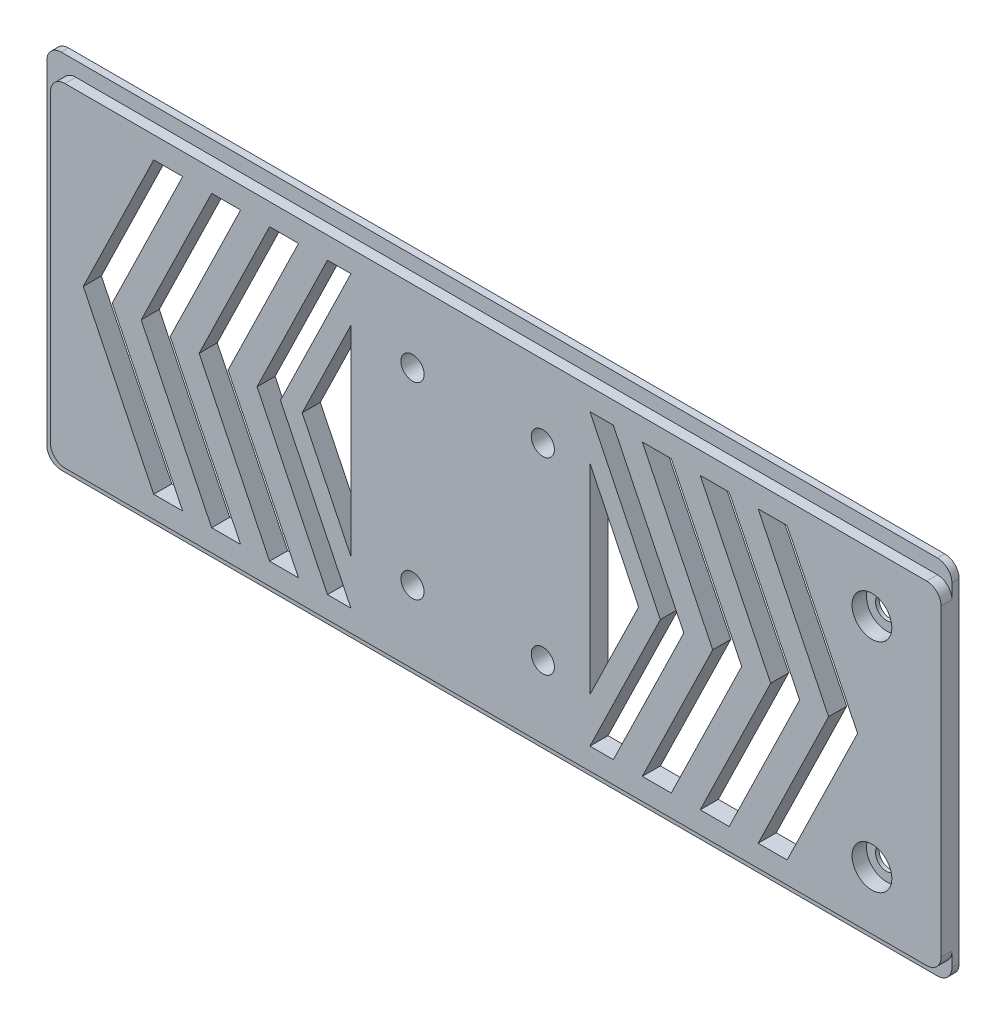
SolidWorks part; units mm, degrees
ref_plane "Plano frontal" through (0, 0, 0) normal (0, 0, 1) x (1, 0, 0)
ref_plane "Plano superior" through (0, 0, 0) normal (0, 1, 0) x (1, 0, 0)
ref_plane "Plano direito" through (0, 0, 0) normal (1, 0, 0) x (0, 0, -1)
sketch "Esboço1" plane through (0, 0, 0) normal (0, 0, 1) x (1, 0, 0)
  line L1 (-17.8424, 34.9053) -> (107.1576, 34.9053)
  line L2 (-17.8424, 34.9053) -> (-17.8424, -15.0947)
  line L3 (-17.8424, -15.0947) -> (107.1576, -15.0947)
  line L4 (107.1576, 34.9053) -> (107.1576, -15.0947)
  dimension "D1" = 50
  dimension "D2" = 125
extrude "Ressalto-extrusão1" add sketch "Esboço1" along normal blind 2.5
sketch "Esboço2" plane through (0, 0, 2.5) normal (0, 0, 1) x (1, 0, 0)
  line L1 (31.1576, 25.9053) -> (55.1576, 25.9053)
  line L2 (31.1576, 25.9053) -> (31.1576, -6.0947)
  line L3 (31.1576, -6.0947) -> (55.1576, -6.0947)
  line L4 (55.1576, 25.9053) -> (55.1576, -6.0947)
  line L8 (107.1576, -15.0947) -> (107.1576, 34.9053) construction
  line L9 (-17.8424, -15.0947) -> (107.1576, -15.0947) construction
  line L10 (43.1576, 25.9053) -> (43.1576, -6.0947) construction
  line L11 (31.1576, 9.9053) -> (43.1576, 9.9053) construction
  line L12 (55.1576, 25.9053) -> (107.1576, 25.9053) construction
  line L15 (55.1576, 25.9053) -> (55.1576, 34.9053) construction
  line L16 (107.1576, 34.9053) -> (-17.8424, 34.9053) construction
  line L17 (55.1576, -6.0947) -> (55.1576, -15.0947) construction
  circle A0 centre (34.1576, 22.9053) radius 1.6
  circle A1 centre (34.1576, -3.0947) radius 1.6
  circle A2 centre (52.1576, -3.0947) radius 1.6
  circle A3 centre (52.1576, 22.9053) radius 1.6
  dimension "D5" = 3
  dimension "D1" = 24
  dimension "D2" = 32
  dimension "D3" = 52
  dimension "D6" = 3
extrude "Corte-extrusão2" cut sketch "Esboço2" against normal blind 2.5 contours A2 | A1 | A3 | A0
sketch "Esboço3" plane through (0, 0, 2.5) normal (0, 0, 1) x (1, 0, 0)
  line L0 (-17.8424, 9.9053) -> (107.1576, 9.9053) construction
  line L1 (-17.8424, 34.9053) -> (-17.8424, -15.0947) construction
  line L2 (107.1576, -15.0947) -> (107.1576, 34.9053) construction
  line L4 (-17.8424, 34.9053) -> (107.1576, 34.9053)
  line L5 (-17.8424, 34.9053) -> (-17.8424, 32.9053)
  line L6 (-15.8424, 32.9053) -> (107.1576, 32.9053)
  line L7 (107.1576, 34.9053) -> (107.1576, 32.9053)
  line L8 (107.1576, -15.0947) -> (107.1576, -13.0947)
  line L9 (-17.8424, -15.0947) -> (107.1576, -15.0947)
  line L10 (-17.8424, -15.0947) -> (-17.8424, -13.0947)
  line L11 (-17.8424, 32.9053) -> (-17.8424, -13.0947)
  line L12 (-17.8424, 34.9053) -> (-15.8424, 34.9053)
  line L13 (-17.8424, 34.9053) -> (-17.8424, -15.0947)
  line L14 (-17.8424, -15.0947) -> (-15.8424, -15.0947)
  line L15 (-15.8424, 32.9053) -> (-15.8424, -13.0947)
  line L16 (-15.8424, -13.0947) -> (107.1576, -13.0947)
  point P18 (-15.8424, 32.9053)
  line M17 (-17.8424, 34.9053) -> (-17.8424, -15.0947)
  line M18 (-17.8424, -15.0947) -> (107.1576, -15.0947)
  line M19 (107.1576, -15.0947) -> (107.1576, 34.9053)
  line M20 (107.1576, 34.9053) -> (-17.8424, 34.9053)
  dimension "D1" = 2
  dimension "D2" = 2
extrude "Corte-extrusão3" cut sketch "Esboço3" against normal blind 1.5 contours L0 L15 L6 L4 M17 M19 M20 | L0 L13 L9 L16 L15 M17 M18 M19 region at (-16.5677, 21.4053, 2.5) region at (-16.8424, 8.6306, 2.5)
sketch "Esboço4" plane through (0, 0, 2.5) normal (0, 0, 1) x (1, 0, 0)
  line L0 (42.1576, 32.9053) -> (42.1576, -13.0947) construction
  line L7 (15.9251, 9.9053) -> (25.654, 29.9053)
  line L16 (15.9251, 9.9053) -> (25.654, -10.0947)
  line L18 (12.6906, 9.9053) -> (22.4196, 29.9053)
  line L19 (22.4196, 29.9053) -> (25.654, 29.9053)
  line L20 (25.654, 23.7382) -> (18.9251, 9.9053)
  line L21 (18.9251, 9.9053) -> (25.654, -3.9275)
  line L24 (-15.8424, 32.9053) -> (-15.8424, -13.0947) construction
  line L25 (8.6906, 9.9053) -> (18.4196, 29.9053)
  line L26 (18.4196, -10.0947) -> (8.6906, 9.9053)
  line L27 (4.6906, 9.9053) -> (14.4196, 29.9053)
  line L28 (14.4196, -10.0947) -> (4.6906, 9.9053)
  line L29 (0.6906, 9.9053) -> (10.4196, 29.9053)
  line L30 (10.4196, -10.0947) -> (0.6906, 9.9053)
  line L31 (-3.3094, 9.9053) -> (6.4196, 29.9053)
  line L32 (6.4196, -10.0947) -> (-3.3094, 9.9053)
  line L33 (-7.3094, 9.9053) -> (2.4196, 29.9053)
  line L34 (2.4196, -10.0947) -> (-7.3094, 9.9053)
  line L35 (-11.3094, 9.9053) -> (-1.5804, 29.9053)
  line L36 (-1.5804, -10.0947) -> (-11.3094, 9.9053)
  line L38 (-12.9532, 9.9053) -> (-11.3094, 9.9053) construction
  line L41 (-1.5804, 29.9053) -> (2.4196, 29.9053)
  line L42 (6.4196, 29.9053) -> (10.4196, 29.9053)
  line L43 (14.4196, 29.9053) -> (18.4196, 29.9053)
  line L46 (-1.5804, -10.0947) -> (2.4196, -10.0947)
  line L47 (6.4196, -10.0947) -> (10.4196, -10.0947)
  line L48 (14.4196, -10.0947) -> (18.4196, -10.0947)
  line L50 (25.654, 23.7382) -> (25.654, -3.9275)
  line L51 (25.654, -3.9275) -> (25.654, 23.7382)
  line L53 (12.6906, 9.9053) -> (22.4196, -10.0947)
  line L54 (85.8956, -10.0947) -> (95.6245, 9.9053)
  line L55 (25.654, -10.0947) -> (22.4196, -10.0947)
  line L57 (14.4196, -10.0947) -> (18.4196, -10.0947)
  line L58 (6.4196, -10.0947) -> (10.4196, -10.0947)
  line L59 (-1.5804, -10.0947) -> (2.4196, -10.0947)
  line L61 (95.6245, 9.9053) -> (85.8956, 29.9053)
  line L62 (85.8956, 29.9053) -> (81.8956, 29.9053)
  line L63 (91.6245, 9.9053) -> (81.8956, 29.9053)
  line L64 (81.8956, -10.0947) -> (91.6245, 9.9053)
  line L65 (85.8956, -10.0947) -> (81.8956, -10.0947)
  line L66 (77.8956, -10.0947) -> (87.6245, 9.9053)
  line L67 (87.6245, 9.9053) -> (77.8956, 29.9053)
  line L68 (77.8956, 29.9053) -> (73.8956, 29.9053)
  line L69 (83.6245, 9.9053) -> (73.8956, 29.9053)
  line L70 (73.8956, -10.0947) -> (83.6245, 9.9053)
  line L71 (77.8956, -10.0947) -> (73.8956, -10.0947)
  line L72 (69.8956, -10.0947) -> (79.6245, 9.9053)
  line L73 (79.6245, 9.9053) -> (69.8956, 29.9053)
  line L74 (69.8956, 29.9053) -> (65.8956, 29.9053)
  line L75 (75.6245, 9.9053) -> (65.8956, 29.9053)
  line L76 (65.8956, -10.0947) -> (75.6245, 9.9053)
  line L77 (69.8956, -10.0947) -> (65.8956, -10.0947)
  line L78 (71.6245, 9.9053) -> (61.8956, 29.9053)
  line L79 (61.8956, 29.9053) -> (58.6611, 29.9053)
  line L80 (68.3901, 9.9053) -> (58.6611, 29.9053)
  line L81 (68.3901, 9.9053) -> (58.6611, -10.0947)
  line L82 (58.6611, -10.0947) -> (61.8956, -10.0947)
  line L83 (71.6245, 9.9053) -> (61.8956, -10.0947)
  line L84 (65.3901, 9.9053) -> (58.6611, -3.9275)
  line L85 (58.6611, 23.7382) -> (65.3901, 9.9053)
  line L86 (58.6611, -3.9275) -> (58.6611, 23.7382)
  line L89 (95.6245, 9.9053) -> (105.5606, 9.9053) construction
  dimension "D3" = 58
  dimension "D1" = 40
  dimension "D2" = 3
extrude "Corte-extrusão5" cut sketch "Esboço4" against normal through all both and the other way through all contours L86 L84 L85 | L83 L78 L79 L80 L81 L82 | L77 L72 L73 L74 L75 L76 | L71 L66 L67 L68 L69 L70 | L65 L54 L61 L62 L63 L64 | L51 L20 L21 | L53 L55 L16 L7 L19 L18 | L48 L26 L25 L43 L27 L28 | L47 L30 L29 L42 L31 L32 | L46 L34 L33 L41 L35 L36 region at (83.8956, -9.6718, 2.5) region at (75.8956, -9.6718, 2.5) region at (67.8956, -9.6718, 2.5) region at (66.3819, 0.0893, 2.5) region at (60.9041, 9.9053, 2.5)
sketch "Esboço12" plane through (0, 0, 2.5) normal (0, 0, 1) x (1, 0, 0)
  line L0 (107.1576, -13.0947) -> (107.1576, 32.9053) construction
  line L1 (-15.8424, 32.9053) -> (107.1576, 32.9053) construction
  line L2 (95.6245, 9.9053) -> (107.1576, 9.9053) construction
  circle A0 centre (97.6076, 24.9053) radius 2.75
  circle A1 centre (97.6076, -5.0947) radius 2.75
  point P0 (97.6076, 24.9053)
  point P8 (97.6076, -5.0947)
  point P13 (94.8576, 24.9053)
  point P14 (94.8576, -5.0947)
  dimension "D3" = 5.5
  dimension "D4" = 5.5
  dimension "D1" = 12.3
  dimension "D2" = 8
extrude "Corte-extrusão6" cut sketch "Esboço12" against normal blind 2
sketch "Esboço19" plane through (0, 0, 0.5) normal (0, 0, 1) x (1, 0, 0)
  circle A0 centre (97.6076, 24.9053) radius 1.5
  circle A1 centre (97.6076, -5.0947) radius 1.5
extrude "Corte-extrusão7" cut sketch "Esboço19" against normal blind 2
fillet "Filete1" radius 2 8 edges at (-17.8424, -15.0947, 0.5) (-15.8424, -13.0947, 1.75) (-17.8424, 34.9053, 0.5) (-15.8424, 32.9053, 1.75) (107.1576, -15.0947, 0.5) (107.1576, -13.0947, 1.75) (107.1576, 32.9053, 1.75) (107.1576, 34.9053, 0.5)
